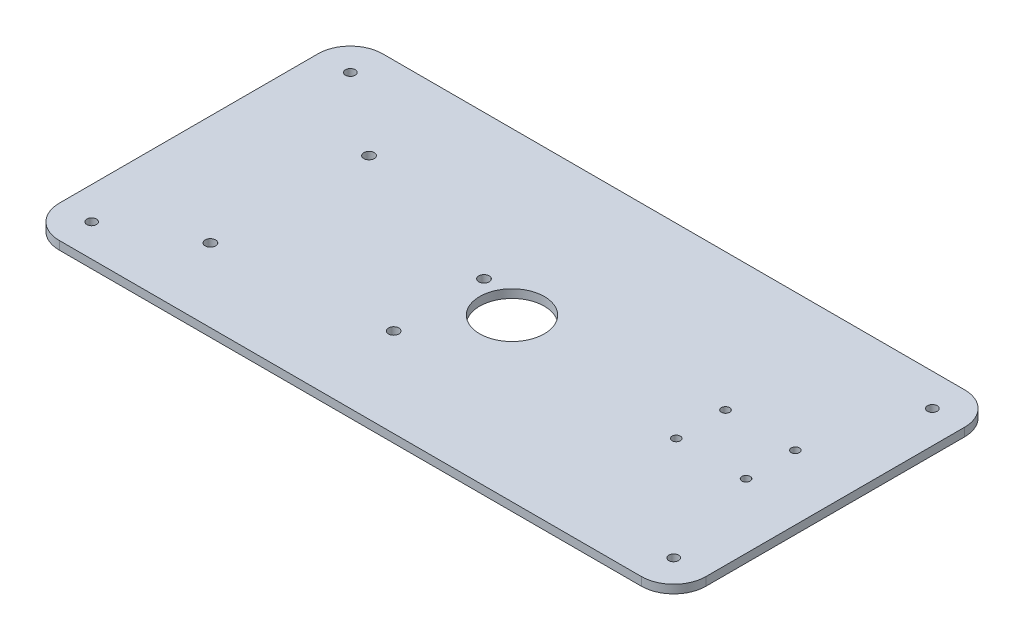
SolidWorks part; units mm, degrees
ref_plane "Front Plane" through (0, 0, 0) normal (0, 0, 1) x (1, 0, 0)
ref_plane "Top Plane" through (0, 0, 0) normal (0, 1, 0) x (1, 0, 0)
ref_plane "Right Plane" through (0, 0, 0) normal (1, 0, 0) x (0, 0, -1)
sketch "Sketch1" plane through (0, 0, 0) normal (0, 1, 0) x (1, 0, 0)
  line L1 (0, 0) -> (200, 0)
  line L2 (0, 0) -> (0, -100)
  line L3 (0, -100) -> (200, -100)
  line L4 (200, 0) -> (200, -100)
  dimension "D1" = 100
  dimension "D2" = 200
extrude "Boss-Extrude1" add sketch "Sketch1" along normal blind 2.6 contours L1 L4 L3 L2
fillet "Fillet1" radius 10 4 edges at (0, 1.3, 0) (0, 1.3, 100) (200, 1.3, 100) (200, 1.3, 0)
sketch "Sketch6" plane through (0, 0, 0) normal (0, -1, 0) x (1, 0, 0)
  line L0 (200, 10) -> (200, 90) construction
  line L1 (10, 0) -> (190, 0) construction
  circle A0 centre (190, 10) radius 1.5
  dimension "D1" = 3
  dimension "D2" = 10
  dimension "D3" = 10
ref_plane "Plane1" through (100, 0, 0) normal (1, 0, 0) x (0, 0, -1)
extrude "Cut-Extrude6" cut sketch "Sketch6" against normal blind 2.6 contours A0
ref_plane "Plane14" through (0, 0, 50) normal (0, 0, 1) x (1, 0, 0)
mirror "Mirror5" about plane through (100, 0, 0) normal (1, 0, 0) of "Cut-Extrude6"
mirror "Mirror6" about plane through (0, 0, 50) normal (0, 0, 1) of "Mirror5"
sketch "Sketch15" plane through (0, 0, 0) normal (0, -1, 0) x (1, 0, 0)
  line L0 (100, 0) -> (100, 100) construction
  line L2 (0, 50) -> (200, 50) construction
  line L4 (0, 10) -> (0, 90) construction
  line L5 (200, 10) -> (200, 90) construction
  line L6 (10, 0) -> (190, 0) construction
  line L7 (10, 100) -> (190, 100) construction
  circle A0 centre (100, 50) radius 10
  dimension "D1" = 20
sketch "Sketch16" plane through (0, 2.6, 0) normal (0, 1, 0) x (1, 0, 0)
  circle A0 centre (35.1575, -29.3715) radius 1.6192
extrude "Cut-Extrude9" cut sketch "Sketch16" against normal blind 10
sketch "Sketch17" plane through (0, 2.6, 0) normal (0, 1, 0) x (1, 0, 0)
  circle A0 centre (85.9447, -44.6115) radius 1.6193
extrude "Cut-Extrude10" cut sketch "Sketch17" against normal through all
sketch "Sketch18" plane through (0, 2.6, 0) normal (0, 1, 0) x (1, 0, 0)
  circle A0 centre (34.0145, -77.2886) radius 1.6193
extrude "Cut-Extrude11" cut sketch "Sketch18" against normal through all
sketch "Sketch19" plane through (0, 2.6, 0) normal (0, 1, 0) x (1, 0, 0)
  circle A0 centre (85.9447, -72.5387) radius 1.6193
extrude "Cut-Extrude12" cut sketch "Sketch19" against normal through all
extrude "Cut-Extrude14" cut sketch "Sketch15" against normal through all contours A0
sketch "Sketch20" plane through (0, 2.6, 0) normal (0, 1, 0) x (1, 0, 0)
  line L0 (-1.43, -50) -> (1.43, -50) construction
  line L1 (158.41, -42.38) -> (158.41, 0) construction
  line L2 (10, 0) -> (190, 0) construction
  line L3 (158.41, 0) -> (158.41, -100) construction
  line L4 (10, -100) -> (190, -100) construction
  line L5 (180, -42.38) -> (180, 0) construction
  line L6 (180, 0) -> (180, -101.354) construction
  line L7 (200, -10) -> (200, -90) construction
  circle A0 centre (158.41, -42.38) radius 1.27
  circle A1 centre (180, -42.38) radius 1.27
  circle A2 centre (158.41, -57.62) radius 1.27
  circle A3 centre (180, -57.62) radius 1.27
  dimension "D1" = 7.62
  dimension "D2" = 7.62
  dimension "D4" = 7.62
  dimension "D7" = 2.54
  dimension "D8" = 2.54
  dimension "D9" = 2.54
  dimension "D10" = 2.54
  dimension "D3" = 21.59
  dimension "D5" = 7.62
  dimension "D6" = 20
extrude "Cut-Extrude15" cut sketch "Sketch20" against normal through all
